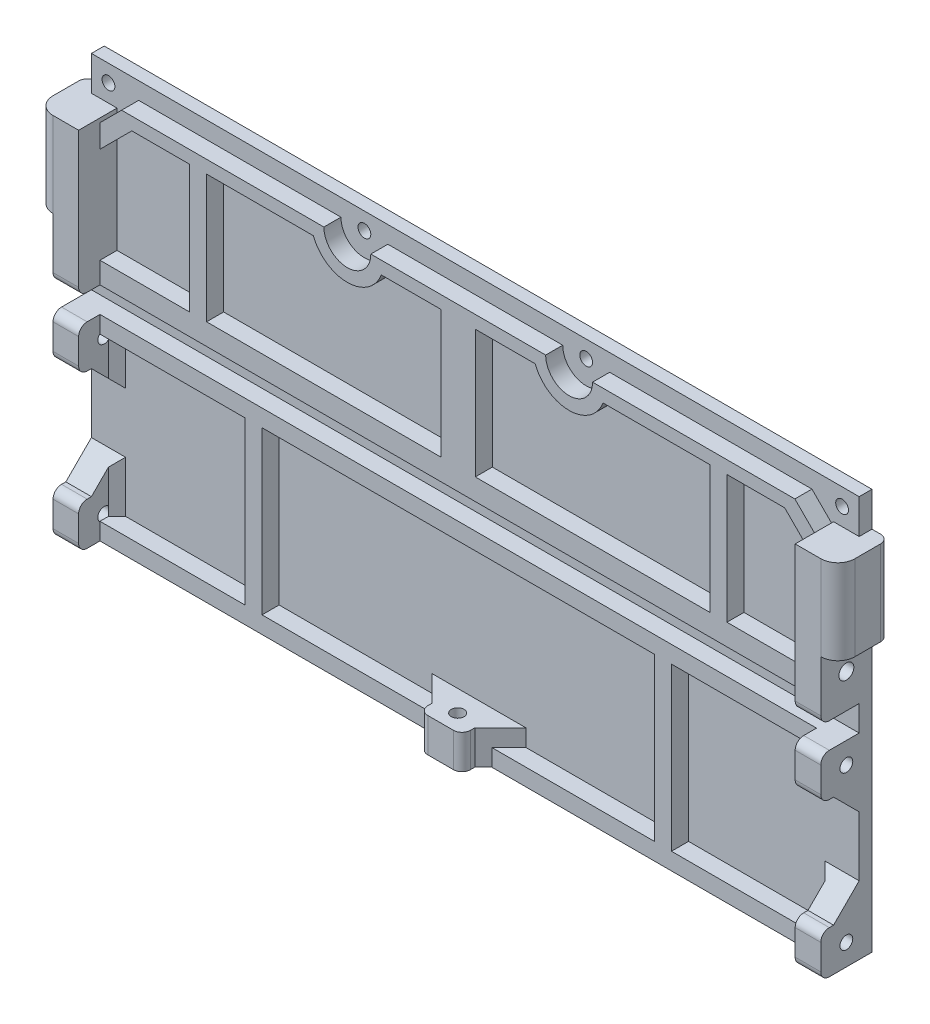
SolidWorks part; units mm, degrees
material "АБС-2020, черный"
ref_plane "Спереди" through (0, 0, 0) normal (0, 0, 1) x (1, 0, 0)
ref_plane "Сверху" through (0, 0, 0) normal (0, 1, 0) x (1, 0, 0)
ref_plane "Справа" through (0, 0, 0) normal (1, 0, 0) x (0, 0, -1)
other "Configuration Table"
sketch "Эскиз1" plane through (0, 0, 0) normal (0, 0, 1) x (1, 0, 0)
  line L1 (0, 0) -> (180, 0)
  line L2 (0, 0) -> (0, -94)
  line L3 (0, -94) -> (180, -94)
  line L4 (180, 0) -> (180, -94)
  dimension "D1" = 94
  dimension "D2" = 180
extrude "Бобышка-Вытянуть1" add sketch "Эскиз1" along normal blind 3
sketch "Эскиз2" plane through (0, 0, 3) normal (0, 0, 1) x (1, 0, 0)
  line L1 (0, -94) -> (6, -94)
  line L2 (0, -94) -> (0, -84)
  line L3 (0, -84) -> (6, -84)
  line L4 (6, -94) -> (6, -84)
  line L5 (180, -94) -> (174, -94)
  line L6 (180, -94) -> (180, -84)
  line L7 (180, -84) -> (174, -84)
  line L8 (174, -94) -> (174, -84)
  line L9 (0, -48) -> (6, -48)
  line L10 (0, -48) -> (0, -58)
  line L11 (0, -58) -> (6, -58)
  line L12 (6, -48) -> (6, -58)
  line L13 (180, -94) -> (180, 0) construction
  line L14 (180, -48) -> (174, -48)
  line L15 (180, -48) -> (180, -58)
  line L16 (180, -58) -> (174, -58)
  line L17 (174, -48) -> (174, -58)
  line L18 (0, -94) -> (180, -94) construction
  line L19 (180, 0) -> (0, 0) construction
  line L20 (180, -8.1) -> (174, -8.1)
  line L21 (180, -8.1) -> (180, -42)
  line L22 (180, -42) -> (174, -42)
  line L23 (174, -8.1) -> (174, -42)
  line L24 (0, -8.1) -> (6, -8.1)
  line L25 (0, -8.1) -> (0, -42)
  line L26 (0, -42) -> (6, -42)
  line L27 (6, -8.1) -> (6, -42)
  line L29 (85.876, -94) -> (95.876, -94)
  line L30 (85.876, -94) -> (85.876, -86)
  line L31 (85.876, -86) -> (95.876, -86)
  line L32 (95.876, -94) -> (95.876, -86)
  point P28 (3, -42)
  point P39 (0, 0)
  point P40 (90.876, -94)
  point P41 (0, 0)
  dimension "D1" = 10
  dimension "D2" = 6
  dimension "D3" = 10
  dimension "D4" = 6
  dimension "D5" = 46
  dimension "D6" = 6
  dimension "D7" = 6
  dimension "D9" = 10
  dimension "D10" = 10
  dimension "D11" = 6
  dimension "D12" = 8.1
  dimension "D13" = 8.1
  dimension "D14" = 6
  dimension "D15" = 10
  dimension "D16" = 5
  dimension "D17" = 8
extrude "Бобышка-Вытянуть2" add sketch "Эскиз2" along normal blind 9
chamfer "Фаска2" distance 6 angle 45 2 edges at (3, -58, 3) (177, -58, 3)
chamfer "Фаска1" distance 6 angle 45 2 edges at (3, -84, 3) (177, -84, 3)
sketch "Эскиз3" plane through (180, 0, 0) normal (1, 0, 0) x (0, 0, -1)
  line L0 (0, -94) -> (0, 0) construction
  line L1 (-12, -94) -> (0, -94) construction
  line L2 (-3, 0) -> (0, 0) construction
  circle A0 centre (-6, -89) radius 1.5
  circle A1 centre (-6, -53) radius 1.5
  circle A2 centre (-6, -34) radius 1.75
  dimension "D1" = 3
  dimension "D4" = 3
  dimension "D7" = 3.5
  dimension "D2" = 6
  dimension "D3" = 5
  dimension "D5" = 36
  dimension "D6" = 34
extrude "Вырез-Вытянуть1" cut sketch "Эскиз3" against normal blind 8
sketch "Эскиз4" plane through (0, 0, 3) normal (0, 0, 1) x (1, 0, 0)
  line L0 (0, -84) -> (0, -94) construction
  line L1 (180, -94) -> (180, -84) construction
  line L2 (180, 0) -> (0, 0) construction
  circle A0 centre (4, -4) radius 1.5
  circle A1 centre (176, -4) radius 1.5
  circle A2 centre (64, -4) radius 1.5
  circle A3 centre (116, -4) radius 1.5
  dimension "D7" = 3
  dimension "D4" = 3
  dimension "D5" = 3
  dimension "D1" = 4
  dimension "D2" = 4
  dimension "D3" = 4
  dimension "D6" = 60
  dimension "D8" = 60
extrude "Вырез-Вытянуть2" cut sketch "Эскиз4" against normal through all
sketch "Эскиз5" plane through (0, 0, 3) normal (0, 0, 1) x (1, 0, 0)
  line L2 (40, -52) -> (40, -90)
  line L4 (44, -52) -> (44, -90)
  line L5 (180, -78) -> (180, -64) construction
  line L7 (136, -52) -> (136, -90)
  line L9 (140, -52) -> (140, -90)
  line L10 (0, -64) -> (0, -78) construction
  line L11 (180, 0) -> (0, 0) construction
  line L13 (27, -4.5) -> (27, -37)
  line L15 (31, -4.5) -> (31, -37)
  line L18 (149, -4.5) -> (149, -37)
  line L20 (153, -4.5) -> (153, -37)
  line L21 (27, -4.5) -> (31, -4.5)
  line L22 (149, -4.5) -> (153, -4.5)
  line L23 (0, 0) -> (0, -8.1) construction
  line L24 (180, -48) -> (180, -42) construction
  line L25 (174, -8.1) -> (174, -42) construction
  line L26 (86, -4.5) -> (94, -4.5)
  line L27 (86, -4.5) -> (86, -37)
  line L29 (94, -4.5) -> (94, -37)
  line L31 (6, -42) -> (6, -37)
  line L32 (6, -37) -> (27, -37)
  line L33 (174, -42) -> (174, -37)
  line L34 (31, -37) -> (86, -37)
  line L35 (94, -37) -> (149, -37)
  line L36 (153, -37) -> (174, -37)
  line L37 (6, -42) -> (174, -42)
  line L39 (6, -48) -> (6, -52)
  line L40 (6, -52) -> (40, -52)
  line L41 (174, -48) -> (174, -52)
  line L42 (174, -48) -> (174, -58) construction
  line L43 (180, -48) -> (174, -48) construction
  line L44 (180, -48) -> (174, -48) construction
  line L45 (44, -52) -> (136, -52)
  line L46 (140, -52) -> (174, -52)
  line L47 (6, -48) -> (174, -48)
  line L48 (6, -90) -> (40, -90)
  line L49 (6, -94) -> (6, -84) construction
  line L50 (174, -84) -> (174, -94) construction
  line L51 (6, -90) -> (6, -94)
  line L53 (44, -90) -> (136, -90)
  line L54 (140, -90) -> (174, -90)
  line L55 (6, -94) -> (174, -94)
  line L56 (174, -94) -> (180, -94) construction
  line L57 (174, -94) -> (174, -90)
  point P5 (174, -94)
  dimension "D12" = 8
  dimension "D2" = 4
  dimension "D3" = 40
  dimension "D4" = 40
  dimension "D7" = 27
  dimension "D8" = 4
  dimension "D9" = 4.5
  dimension "D10" = 4
  dimension "D11" = 27
  dimension "D13" = 55
  dimension "D14" = 55
extrude "Бобышка-Вытянуть3" add sketch "Эскиз5" along normal blind 4
chamfer "Фаска3" distance 2 angle 45 4 edges at (174, -84, 3) (174, -58, 3) (6, -84, 3) (6, -58, 3)
sketch "Эскиз6" plane through (180, 0, 0) normal (1, 0, 0) x (0, 0, -1)
  line L0 (0, -94) -> (0, 0) construction
  line L1 (-12, -8.1) -> (0, -8.1)
  line L2 (-12, -8.1) -> (-12, -28)
  line L3 (-12, -28) -> (0, -28)
  line L4 (0, -8.1) -> (0, -28)
  line L5 (-3, 0) -> (0, 0) construction
  dimension "D1" = 28
  dimension "D2" = 8.1
extrude "Бобышка-Вытянуть4" add sketch "Эскиз6" along normal blind 4
fillet "Скругление1" radius 4 1 edges at (184, -18.05, 12)
sketch "Эскиз7" plane through (0, 0, 0) normal (-1, 0, 0) x (0, 0, 1)
  line L0 (12, -8.1) -> (12, -42) construction
  line L1 (0, -8.1) -> (12, -8.1)
  line L2 (0, -8.1) -> (0, -28)
  line L3 (0, -28) -> (12, -28)
  line L4 (12, -8.1) -> (12, -28)
  line L5 (3, 0) -> (0, 0) construction
  dimension "D1" = 28
extrude "Бобышка-Вытянуть5" add sketch "Эскиз7" along normal blind 4
fillet "Скругление2" radius 4 1 edges at (-4, -18.05, 12)
fillet "Скругление3" radius 2 2 edges at (184, -18.05, 0) (-4, -18.05, 0)
sketch "Эскиз8" plane through (0, -94, 0) normal (0, -1, 0) x (1, 0, 0)
  line L1 (85.876, 12) -> (85.876, 7) construction
  line L2 (0, 0) -> (180, 0) construction
  circle A0 centre (90.876, 8) radius 1.5
  dimension "D3" = 3
  dimension "D2" = 5
  dimension "D4" = 8
extrude "Вырез-Вытянуть3" cut sketch "Эскиз8" against normal blind 10
sketch "Эскиз9" plane through (0, 0, 0) normal (-1, 0, 0) x (0, 0, 1)
  line L0 (0, -28) -> (0, -94) construction
  line L1 (12, -94) -> (0, -94) construction
  circle A0 centre (6, -89) radius 1.5
  circle A1 centre (6, -53) radius 1.5
  point P8 (0, 0)
  dimension "D1" = 3
  dimension "D2" = 3
  dimension "D3" = 36
  dimension "D4" = 6
  dimension "D5" = 5
extrude "Вырез-Вытянуть4" cut sketch "Эскиз9" against normal blind 6
chamfer "Фаска4" distance 6 angle 45 2 edges at (95.876, -88, 3) (85.876, -88, 3)
fillet "Скругление4" radius 2 12 edges at (177, -84, 12) (3, -84, 12) (3, -42, 12) (3, -48, 12) (3, -58, 12) (3, -94, 12) (177, -42, 12) (177, -48, 12) (177, -58, 12) (85.876, -90, 12) (95.876, -90, 12) (177, -94, 12)
sketch "Эскиз10" plane through (0, 0, 3) normal (0, 0, 1) x (1, 0, 0)
  line L0 (11.0731, -4) -> (58.5, -4)
  line L1 (6, -14.4642) -> (13.4642, -7)
  line L2 (6, -37) -> (6, -8.1) construction
  line L3 (13.4642, -7) -> (56.047, -7)
  line L4 (166.5358, -7) -> (174, -14.4642)
  line L5 (174, -8.1) -> (174, -40) construction
  line L6 (174, -14.4642) -> (174, -9.0731)
  line L7 (174, -8.1) -> (174, -37) construction
  line L9 (174, -9.0731) -> (168.9269, -4)
  line L10 (6, -9.0731) -> (11.0731, -4)
  line L11 (69.5, -4) -> (110.5, -4)
  line L12 (71.953, -7) -> (108.047, -7)
  line L13 (6, -40) -> (6, -8.1) construction
  line L14 (123.953, -7) -> (166.5358, -7)
  line L15 (121.5, -4) -> (168.9269, -4)
  line L16 (6, -9.0731) -> (6, -14.4642)
  arc A0 (110.5, -4) -> (121.5, -4) centre (116, -4) ccw
  arc A1 (58.5, -4) -> (69.5, -4) centre (64, -4) ccw
  arc A4 (56.047, -7) -> (71.953, -7) centre (64, -4) ccw
  arc A5 (108.047, -7) -> (123.953, -7) centre (116, -4) ccw
  point P1 (6, -8.1)
  point P12 (6, -9.0731)
  point P26 (174, -9.0731)
  point P35 (0, 0)
  point P36 (0, 0)
  line M8 (6, -8.1) -> (6, -37)
  line M10 (27, -37) -> (27, -4.5)
  line M11 (27, -4.5) -> (31, -4.5)
  line M12 (31, -4.5) -> (31, -37)
  line M14 (86, -37) -> (86, -4.5)
  line M15 (86, -4.5) -> (94, -4.5)
  line M16 (94, -4.5) -> (94, -37)
  line M18 (149, -37) -> (149, -4.5)
  line M19 (149, -4.5) -> (153, -4.5)
  line M20 (153, -4.5) -> (153, -37)
  line M22 (174, -37) -> (174, -8.1)
  dimension "D1" = 17
  dimension "D5" = 17
  dimension "D2" = 3
  dimension "D3" = 45
  dimension "D4" = 45
extrude "Бобышка-Вытянуть6" add sketch "Эскиз10" along normal blind 4 contours L12 A5 L15 A0 L11 A1 L0 L10 L1 L3 A4 M8 M10 M11 M12 M14 M15 M16 | A5 L14 L4 L9 L15 M18 M19 M20 M22 region at (34.7866, -5.6833, 3)
